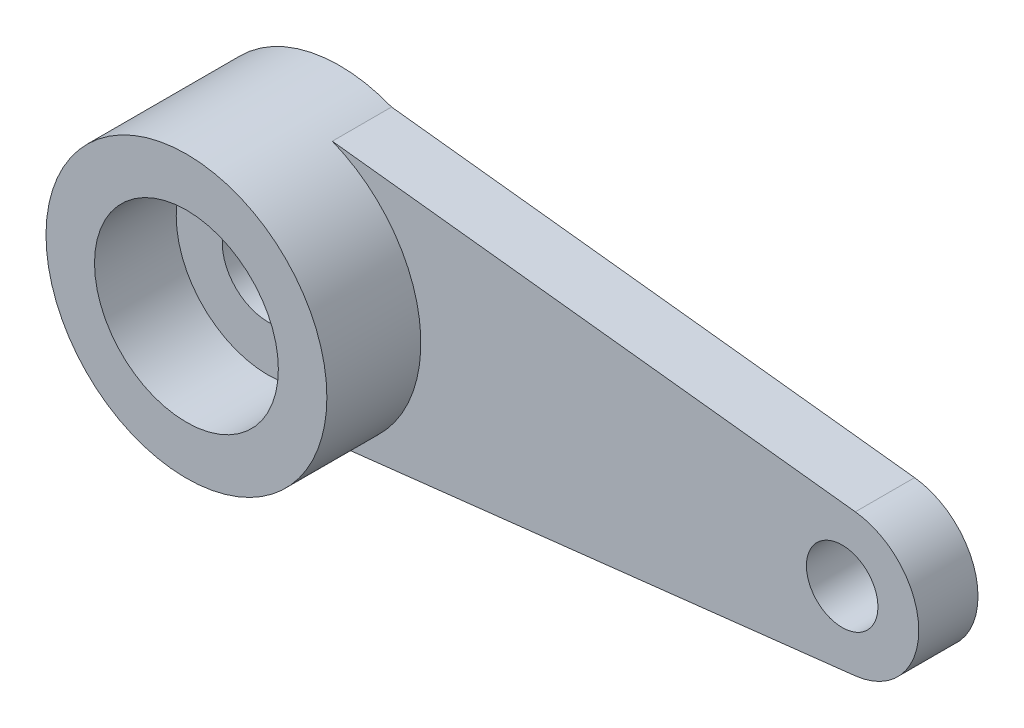
SolidWorks part; units mm, degrees
ref_plane "Front Plane" through (0, 0, 0) normal (0, 0, 1) x (1, 0, 0)
ref_plane "Top Plane" through (0, 0, 0) normal (0, 1, 0) x (1, 0, 0)
ref_plane "Right Plane" through (0, 0, 0) normal (1, 0, 0) x (0, 0, -1)
sketch "Sketch2" plane through (0, 0, 0) normal (0, 0, 1) x (1, 0, 0)
  circle A0 centre (0, 0) radius 3.4925
  dimension "D1" = 6.985
extrude "Boss-Extrude1" add sketch "Sketch2" along normal blind 3.81 contours A0
sketch "Sketch3" plane through (0, 0, 3.81) normal (0, 0, 1) x (1, 0, 0)
  circle A0 centre (0, 0) radius 2.286
  dimension "D1" = 4.572
extrude "Cut-Extrude1" cut sketch "Sketch3" against normal blind 2.032
sketch "Sketch4" plane through (0, 0, 1.778) normal (0, 0, 1) x (1, 0, 0)
  circle A0 centre (0, 0) radius 1.143
  dimension "D1" = 2.286
extrude "Cut-Extrude2" cut sketch "Sketch4" against normal blind 2.2225
sketch "Sketch5" plane through (0, 0, 0) normal (0, 0, -1) x (-1, 0, 0)
  circle A0 centre (0, 0) radius 2.286
  dimension "D1" = 4.572
extrude "Cut-Extrude3" cut sketch "Sketch5" against normal blind 1.016
sketch "Sketch6" plane through (0, 0, 0) normal (0, 0, -1) x (-1, 0, 0)
  line L0 (-1.291, 3.2451) -> (-14.2978, 1.7666)
  line L1 (-14.2978, -1.7666) -> (-1.291, -3.2451)
  circle A0 centre (-13.97, 0) radius 0.889
  circle A2 centre (0, 0) radius 3.4925 construction
  arc A3 (-14.2978, 1.7666) -> (-14.2978, -1.7666) centre (-14.097, 0) ccw
  arc A4 (-1.291, 3.2451) -> (-1.291, -3.2451) centre (0, 0) ccw
  point P11 (-1.7678, 3.012)
  point P12 (-1.3444, -3.2234)
  point P14 (-0.9074, -3.3726)
  point P15 (-14.5413, -1.27)
  point P16 (-15.875, 0)
  dimension "D1" = 13.97
  dimension "D2" = 1.778
  dimension "D3" = 1.778
  dimension "D4" = 15.875
  dimension "D5" = 13.0068
extrude "Boss-Extrude2" add sketch "Sketch6" against normal blind 1.4732
